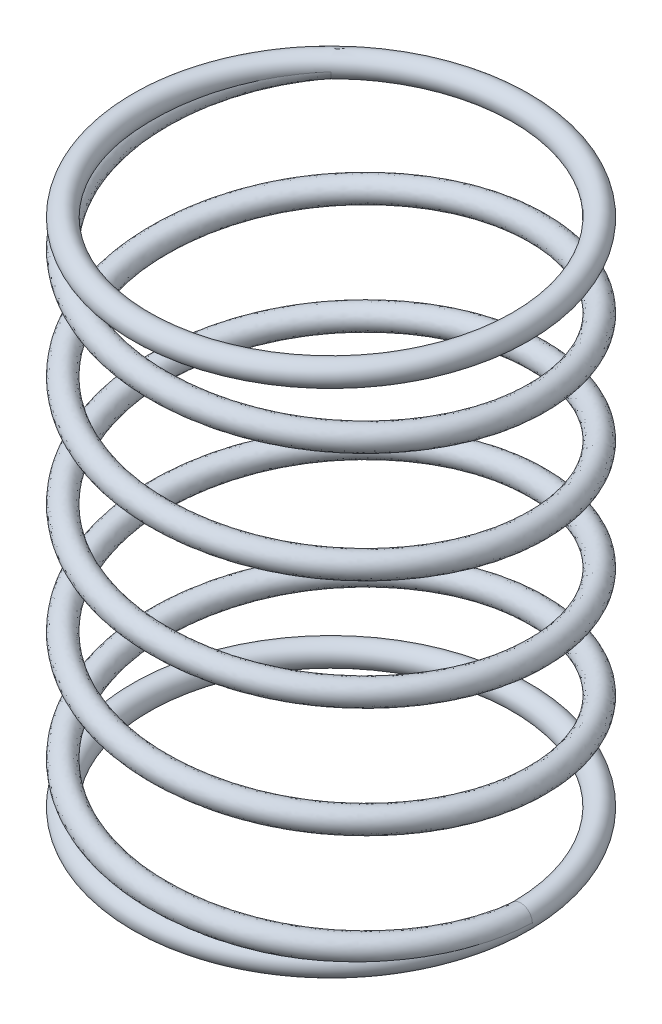
SolidWorks part; units mm, degrees
note: The reader was unsure of these and kept them because the rebuilt part matched: shared geometry of "Sketch1<2>".
ref_plane "Front Plane" through (0, 0, 0) normal (0, 0, 1) x (1, 0, 0)
ref_plane "Top Plane" through (0, 0, 0) normal (0, 1, 0) x (1, 0, 0)
ref_plane "Right Plane" through (0, 0, 0) normal (1, 0, 0) x (0, 0, -1)
sketch "Sketch1" plane through (0, 0, 0) normal (0, 0, 1) x (1, 0, 0)
  line L0 (0, 0) -> (2.75, 0) construction
  line L1 (0, 0) -> (0, 7.0102) construction
  circle A0 centre (2.75, 0) radius 0.1678
  dimension "D1" = 2.75
sketch "Sketch2" plane through (0, 0, 0) normal (0, 1, 0) x (1, 0, 0)
  circle A0 centre (0, 0) radius 2.5
curve "Helix/Spiral1" pitch 1.6 height 8 turns 5
sweep "Sweep1" add profiles "Sketch1" path "Helix/Spiral1"
sketch "Sketch3" plane through (0, 0, 0) normal (0.7071, 0, -0.7071) x (-0.7071, 0, -0.7071)
  circle A1 centre (2.75, 7.4) radius 0.1678
  circle A2 centre (2.75, 7.4) radius 0.1678
  dimension "D1" = 0
revolve "Revolve1" add sketch "Sketch1<2>" angle 360 about L1
sketch "Sketch1<2>" plane through (0, 0, 0) normal (0, 0, 1) x (1, 0, 0) same geometry as "Sketch1"
revolve "Revolve2" add sketch "Sketch3" angle 360 about L1
